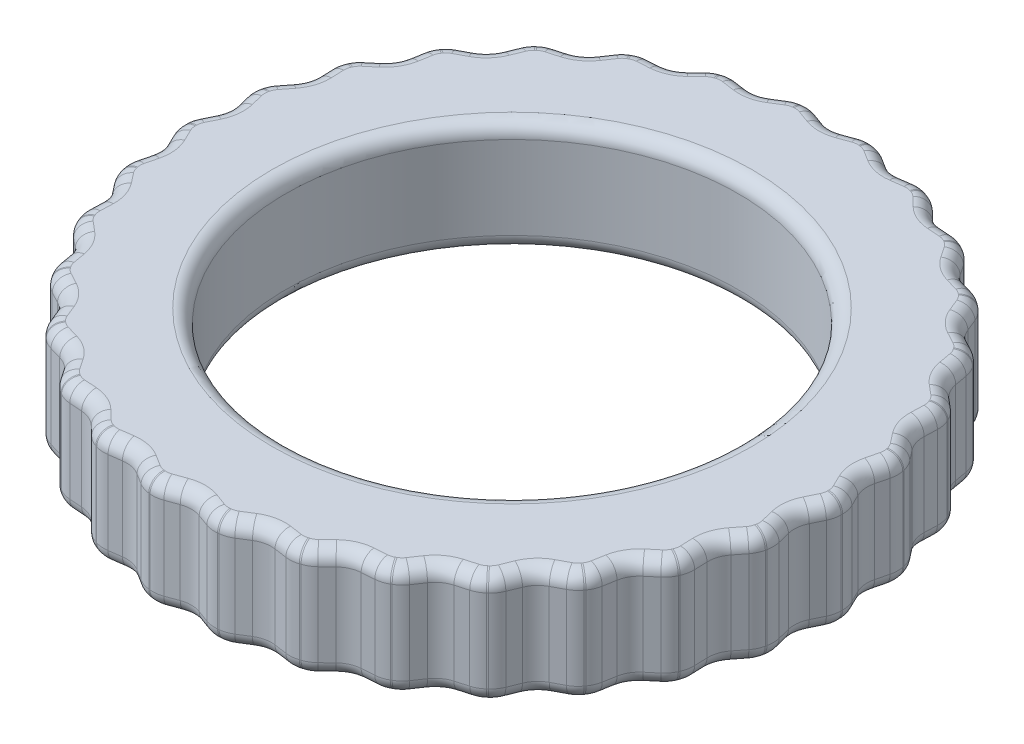
SolidWorks part; units mm, degrees
ref_plane "Front Plane" through (0, 0, 0) normal (0, 0, 1) x (1, 0, 0)
ref_plane "Top Plane" through (0, 0, 0) normal (0, 1, 0) x (1, 0, 0)
ref_plane "Right Plane" through (0, 0, 0) normal (1, 0, 0) x (0, 0, -1)
sketch "Sketch1" plane through (0, 0, 0) normal (0, 1, 0) x (1, 0, 0)
  circle A0 centre (0, 0) radius 16.325
  circle A1 centre (0, 0) radius 23.825
  dimension "D1" = 32.65
  dimension "D2" = 7.5
extrude "Boss-Extrude1" add sketch "Sketch1" along normal blind 8
sketch "Sketch2" plane through (0, 0, 0) normal (0, 1, 0) x (1, 0, 0)
  line L0 (0, -23.825) -> (0, -23.025) construction
  line L1 (0, -23.025) -> (-4.4815, -24.6561)
  line L2 (-4.4815, -24.6561) -> (4.4815, -24.6561)
  line L3 (4.4815, -24.6561) -> (0, -23.025)
  circle A0 centre (0, 0) radius 23.825 construction
  circle A1 centre (0, 0) radius 23.825
  dimension "D1" = 0.8
  dimension "D2" = 70
  dimension "D3" = 70
extrude "Cut-Extrude2" cut sketch "Sketch2" along normal blind 8 contours A1 L1 L2 L3 | L1 L2 L3 region at (0, 0, 24.2771)
fillet "Fillet2" radius 2 3 edges at (-1.9731, 4, 23.7432) (1.9731, 4, 23.7432) (0, 4, 23.025)
pattern_circular "CirPattern1" count 30 over 360 about axis through (0, 8, 0) along (0, 1, 0) of "Cut-Extrude2", "Fillet2"
fillet "Fillet1" radius 1 340 edges at (8.5095, 0, 21.8606) (10.5516, 0, 20.9514) (12.8687, 0, 19.6137) (14.6771, 0, 18.2998) (16.6654, 0, 16.5095) (18.1611, 0, 14.8484) (19.7337, 0, 12.6838) (20.8514, 0, 10.748) (21.9396, 0, 8.3038) (22.6303, 0, 6.1779) (23.1866, 0, 3.5608) (23.4203, 0, 1.3378) (23.4203, 0, -1.3378) (23.1866, 0, -3.5608) (22.6303, 0, -6.1779) (21.9396, 0, -8.3038) (20.8514, 0, -10.748) (19.7337, 0, -12.6838) (18.1611, 0, -14.8484) (16.6654, 0, -16.5095) (14.6771, 0, -18.2998) (12.8687, 0, -19.6137) (10.5516, 0, -20.9514) (8.5095, 0, -21.8606) (5.965, 0, -22.6874) (3.7785, 0, -23.1521) (1.1177, 0, -23.4318) (-1.1177, 0, -23.4318) (-3.7785, 0, -23.1521) (-5.965, 0, -22.6874) (-8.5095, 0, -21.8606) (-10.5516, 0, -20.9514) (-12.8687, 0, -19.6137) (-14.6771, 0, -18.2998) (-16.6654, 0, -16.5095) (-18.1611, 0, -14.8484) (-19.7337, 0, -12.6838) (-20.8514, 0, -10.748) (-21.9396, 0, -8.3038) (-22.6303, 0, -6.1779) (-23.1866, 0, -3.5608) (-23.4203, 0, -1.3378) (-23.4203, 0, 1.3378) (-23.1866, 0, 3.5608) (-22.6303, 0, 6.1779) (-21.9396, 0, 8.3038) (-20.8514, 0, 10.748) (-19.7337, 0, 12.6838) (-18.1611, 0, 14.8484) (-16.6654, 0, 16.5095) (-14.6771, 0, 18.2998) (-12.8687, 0, 19.6137) (-10.5516, 0, 20.9514) (-8.5095, 0, 21.8606) (-5.965, 0, 22.6874) (-3.7785, 0, 23.1521) (-1.1177, 0, 23.4318) (1.1177, 0, 23.4318) (3.7785, 0, 23.1521) (5.965, 0, 22.6874) (0, 0, 16.325) (1.1177, 8, 23.4318) (-1.1177, 8, 23.4318) (-3.7785, 8, 23.1521) (-5.965, 8, 22.6874) (-8.5095, 8, 21.8606) (-10.5516, 8, 20.9514) (-12.8687, 8, 19.6137) (-14.6771, 8, 18.2998) (-16.6654, 8, 16.5095) (-18.1611, 8, 14.8484) (-19.7337, 8, 12.6838) (-20.8514, 8, 10.748) (-21.9396, 8, 8.3038) (-22.6303, 8, 6.1779) (-23.1866, 8, 3.5608) (-23.4203, 8, 1.3378) (-23.4203, 8, -1.3378) (-23.1866, 8, -3.5608) (-22.6303, 8, -6.1779) (-21.9396, 8, -8.3038) (-20.8514, 8, -10.748) (-19.7337, 8, -12.6838) (-18.1611, 8, -14.8484) (-16.6654, 8, -16.5095) (-14.6771, 8, -18.2998) (-12.8687, 8, -19.6137) (-10.5516, 8, -20.9514) (-8.5095, 8, -21.8606) (-5.965, 8, -22.6874) (-3.7785, 8, -23.1521) (-1.1177, 8, -23.4318) (1.1177, 8, -23.4318) (3.7785, 8, -23.1521) (5.965, 8, -22.6874) (8.5095, 8, -21.8606) (10.5516, 8, -20.9514) (12.8687, 8, -19.6137) (14.6771, 8, -18.2998) (16.6654, 8, -16.5095) (18.1611, 8, -14.8484) (19.7337, 8, -12.6838) (20.8514, 8, -10.748) (21.9396, 8, -8.3038) (22.6303, 8, -6.1779) (23.1866, 8, -3.5608) (23.4203, 8, -1.3378) (23.4203, 8, 1.3378) (23.1866, 8, 3.5608) (22.6303, 8, 6.1779) (21.9396, 8, 8.3038) (20.8514, 8, 10.748) (19.7337, 8, 12.6838) (18.1611, 8, 14.8484) (16.6654, 8, 16.5095) (14.6771, 8, 18.2998) (12.8687, 8, 19.6137) (10.5516, 8, 20.9514) (8.5095, 8, 21.8606) (5.965, 8, 22.6874) (3.7785, 8, 23.1521) (0, 8, 16.325) (-1.9895, 0, 23.6951) (0, 0, 23.1534) (1.9895, 0, 23.6951) (4.8139, 0, 22.6474) (6.8725, 0, 22.7636) (9.4173, 0, 21.1516) (11.4551, 0, 20.8373) (13.6092, 0, 18.7315) (15.5371, 0, 18.0003) (17.2063, 0, 15.4926) (18.9401, 0, 14.3766) (20.0514, 0, 11.5767) (21.5153, 0, 10.1246) (22.0201, 0, 7.1548) (23.1501, 0, 5.4301) (23.0265, 0, 2.4202) (23.7732, 0, 0.4982) (23.0265, 0, -2.4202) (23.3573, 0, -4.4554) (22.0201, 0, -7.1548) (21.9206, 0, -9.2143) (20.0514, 0, -11.5767) (19.5258, 0, -13.5705) (17.2063, 0, -15.4926) (16.2777, 0, -17.3335) (13.6092, 0, -18.7315) (12.3181, 0, -20.3391) (9.4173, 0, -21.1516) (7.8202, 0, -22.4557) (4.8139, 0, -22.6474) (2.9805, 0, -23.5909) (0, 0, -23.1534) (-1.9895, 0, -23.6951) (-4.8139, 0, -22.6474) (-6.8725, 0, -22.7636) (-9.4173, 0, -21.1516) (-11.4551, 0, -20.8373) (-13.6092, 0, -18.7315) (-15.5371, 0, -18.0003) (-17.2063, 0, -15.4926) (-18.9401, 0, -14.3766) (-20.0514, 0, -11.5767) (-21.5153, 0, -10.1246) (-22.0201, 0, -7.1548) (-23.1501, 0, -5.4301) (-23.0265, 0, -2.4202) (-23.7732, 0, -0.4982) (-23.0265, 0, 2.4202) (-23.3573, 0, 4.4554) (-22.0201, 0, 7.1548) (-21.9206, 0, 9.2143) (-20.0514, 0, 11.5767) (-19.5258, 0, 13.5705) (-17.2063, 0, 15.4926) (-16.2777, 0, 17.3335) (-13.6092, 0, 18.7315) (-12.3181, 0, 20.3391) (-9.4173, 0, 21.1516) (-7.8202, 0, 22.4557) (-4.8139, 0, 22.6474) (-9.4173, 8, 21.1516) (-12.3181, 8, 20.3391) (-13.6092, 8, 18.7315) (-16.2777, 8, 17.3335) (-17.2063, 8, 15.4926) (-19.5258, 8, 13.5705) (-20.0514, 8, 11.5767) (-21.9206, 8, 9.2143) (-22.0201, 8, 7.1548) (-23.3573, 8, 4.4554) (-23.0265, 8, 2.4202) (-23.7732, 8, -0.4982) (-23.0265, 8, -2.4202) (-23.1501, 8, -5.4301) (-22.0201, 8, -7.1548) (-21.5153, 8, -10.1246) (-20.0514, 8, -11.5767) (-18.9401, 8, -14.3766) (-17.2063, 8, -15.4926) (-15.5371, 8, -18.0003) (-13.6092, 8, -18.7315) (-11.4551, 8, -20.8373) (-9.4173, 8, -21.1516) (-6.8725, 8, -22.7636) (-4.8139, 8, -22.6474) (-1.9895, 8, -23.6951) (0, 8, -23.1534) (2.9805, 8, -23.5909) (4.8139, 8, -22.6474) (7.8202, 8, -22.4557) (9.4173, 8, -21.1516) (12.3181, 8, -20.3391) (13.6092, 8, -18.7315) (16.2777, 8, -17.3335) (17.2063, 8, -15.4926) (19.5258, 8, -13.5705) (20.0514, 8, -11.5767) (21.9206, 8, -9.2143) (22.0201, 8, -7.1548) (23.3573, 8, -4.4554) (23.0265, 8, -2.4202) (23.7732, 8, 0.4982) (23.0265, 8, 2.4202) (23.1501, 8, 5.4301) (22.0201, 8, 7.1548) (21.5153, 8, 10.1246) (20.0514, 8, 11.5767) (18.9401, 8, 14.3766) (17.2063, 8, 15.4926) (15.5371, 8, 18.0003) (13.6092, 8, 18.7315) (11.4551, 8, 20.8373) (9.4173, 8, 21.1516) (6.8725, 8, 22.7636) (4.8139, 8, 22.6474) (1.9895, 8, 23.6951) (0, 8, 23.1534) (-1.9895, 8, 23.6951) (-4.8139, 8, 22.6474) (-7.8202, 8, 22.4557) (-2.9805, 0, 23.5909) (2.9805, 0, 23.5909) (7.8202, 0, 22.4557) (12.3181, 0, 20.3391) (16.2777, 0, 17.3335) (19.5258, 0, 13.5705) (21.9206, 0, 9.2143) (23.3573, 0, 4.4554) (23.7732, 0, -0.4982) (23.1501, 0, -5.4301) (21.5153, 0, -10.1246) (18.9401, 0, -14.3766) (15.5371, 0, -18.0003) (11.4551, 0, -20.8373) (6.8725, 0, -22.7636) (1.9895, 0, -23.6951) (-2.9805, 0, -23.5909) (-7.8202, 0, -22.4557) (-12.3181, 0, -20.3391) (-16.2777, 0, -17.3335) (-19.5258, 0, -13.5705) (-21.9206, 0, -9.2143) (-23.3573, 0, -4.4554) (-23.7732, 0, 0.4982) (-23.1501, 0, 5.4301) (-21.5153, 0, 10.1246) (-18.9401, 0, 14.3766) (-15.5371, 0, 18.0003) (-11.4551, 0, 20.8373) (-6.8725, 0, 22.7636) (-11.4551, 8, 20.8373) (-15.5371, 8, 18.0003) (-18.9401, 8, 14.3766) (-21.5153, 8, 10.1246) (-23.1501, 8, 5.4301) (-23.7732, 8, 0.4982) (-23.3573, 8, -4.4554) (-21.9206, 8, -9.2143) (-19.5258, 8, -13.5705) (-16.2777, 8, -17.3335) (-12.3181, 8, -20.3391) (-7.8202, 8, -22.4557) (-2.9805, 8, -23.5909) (1.9895, 8, -23.6951) (6.8725, 8, -22.7636) (11.4551, 8, -20.8373) (15.5371, 8, -18.0003) (18.9401, 8, -14.3766) (21.5153, 8, -10.1246) (23.1501, 8, -5.4301) (23.7732, 8, -0.4982) (23.3573, 8, 4.4554) (21.9206, 8, 9.2143) (19.5258, 8, 13.5705) (16.2777, 8, 17.3335) (12.3181, 8, 20.3391) (7.8202, 8, 22.4557) (2.9805, 8, 23.5909) (-2.9805, 8, 23.5909) (-6.8725, 8, 22.7636) (-2.4904, 0, 23.6945) (2.4904, 0, 23.6945) (7.3623, 0, 22.6589) (11.9125, 0, 20.6331) (15.942, 0, 17.7054) (19.2748, 0, 14.004) (21.7652, 0, 9.6905) (23.3044, 0, 4.9535) (23.825, 0, 0) (23.3044, 0, -4.9535) (21.7652, 0, -9.6905) (19.2748, 0, -14.004) (15.942, 0, -17.7054) (11.9125, 0, -20.6331) (7.3623, 0, -22.6589) (2.4904, 0, -23.6945) (-2.4904, 0, -23.6945) (-7.3623, 0, -22.6589) (-11.9125, 0, -20.6331) (-15.942, 0, -17.7054) (-19.2748, 0, -14.004) (-21.7652, 0, -9.6905) (-23.3044, 0, -4.9535) (-23.825, 0, 0) (-23.3044, 0, 4.9535) (-21.7652, 0, 9.6905) (-19.2748, 0, 14.004) (-15.942, 0, 17.7054) (-11.9125, 0, 20.6331) (-7.3623, 0, 22.6589) (-11.9125, 8, 20.6331) (-15.942, 8, 17.7054) (-19.2748, 8, 14.004) (-21.7652, 8, 9.6905) (-23.3044, 8, 4.9535) (-23.825, 8, 0) (-23.3044, 8, -4.9535) (-21.7652, 8, -9.6905)
